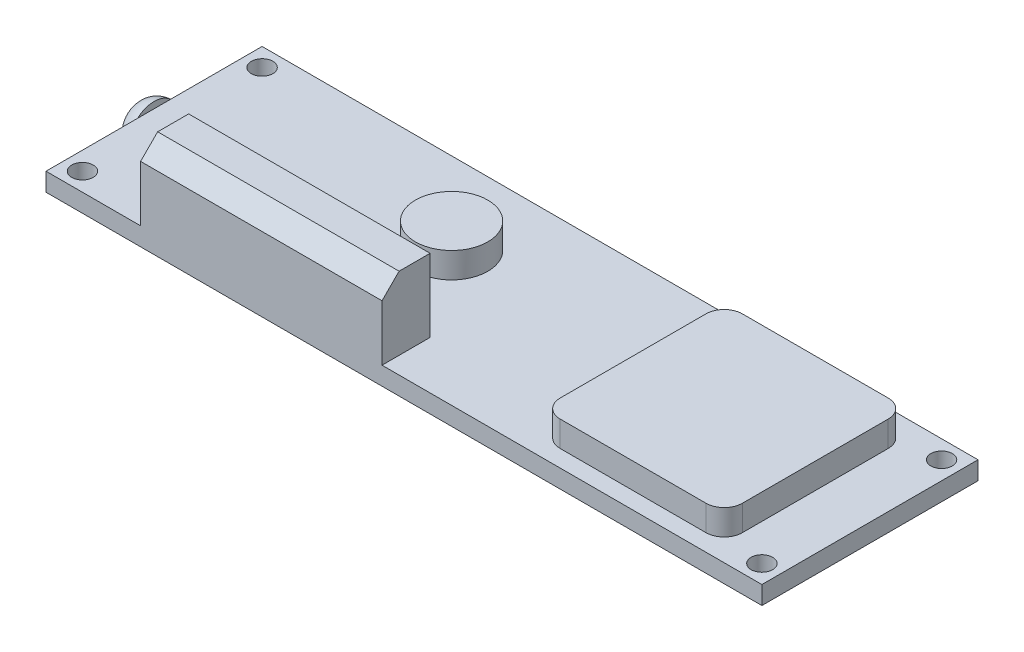
SolidWorks part; units mm, degrees
ref_plane "Front Plane" through (0, 0, 0) normal (0, 0, 1) x (1, 0, 0)
ref_plane "Top Plane" through (0, 0, 0) normal (0, 1, 0) x (1, 0, 0)
ref_plane "Right Plane" through (0, 0, 0) normal (1, 0, 0) x (0, 0, -1)
sketch "Sketch1" plane through (0, 0, 0) normal (0, 1, 0) x (1, 0, 0)
  line L1 (0, 0) -> (99.7966, 0)
  line L2 (0, 0) -> (0, 30.1244)
  line L3 (0, 30.1244) -> (99.7966, 30.1244)
  line L4 (99.7966, 0) -> (99.7966, 30.1244)
  dimension "D1" = 30.1244
  dimension "D2" = 99.7966
extrude "Boss-Extrude1" add sketch "Sketch1" along normal blind 2.54 contours L3 L4 L1 L2
sketch "Sketch2" plane through (0, 2.54, 0) normal (0, 1, 0) x (1, 0, 0)
  line L0 (0, 0) -> (99.7966, 0) construction
  line L1 (13.186, 0) -> (46.8408, 0)
  line L2 (13.186, 0) -> (13.186, 6.7003)
  line L3 (13.186, 6.7003) -> (46.8408, 6.7003)
  line L4 (46.8408, 0) -> (46.8408, 6.7003)
extrude "Boss-Extrude2" add sketch "Sketch2" along normal blind 10.16
sketch "Sketch3" plane through (0, 2.54, 0) normal (0, 1, 0) x (1, 0, 0)
  line L1 (99.7966, 0) -> (99.7966, 30.1244) construction
  line L2 (92.1766, 2.3622) -> (92.1766, 27.7622)
  line L3 (92.1766, 27.7622) -> (66.7766, 27.7622)
  line L4 (66.7766, 27.7622) -> (66.7766, 2.3622)
  line L5 (92.1766, 2.3622) -> (66.7766, 2.3622)
  circle A0 centre (37.8344, 18.7074) radius 5.0456
  point P9 (66.7766, 15.0622)
  point P10 (92.1766, 15.0622)
  dimension "D1" = 25.4
  dimension "D2" = 25.4
  dimension "D3" = 7.62
extrude "Boss-Extrude3" add sketch "Sketch3" along normal blind 3.556
fillet "Fillet1" radius 2.54 4 edges at (92.1766, 4.318, -27.7622) (66.7766, 4.318, -27.7622) (92.1766, 4.318, -2.3622) (66.7766, 4.318, -2.3622)
sketch "Sketch4" plane through (0, 0, 0) normal (-1, 0, 0) x (0, 0, 1)
  line L0 (0, 0) -> (-30.1244, 0) construction
  circle A0 centre (-15.0622, 0) radius 3.429
  dimension "D1" = 6.858
extrude "Boss-Extrude4" add sketch "Sketch4" along normal blind 2.54
fillet "Fillet2" radius 2.54 1 edges at (-2.54, 0, -11.6332)
chamfer "Chamfer1" distance 2.38 angle 45 1 edges at (30.0134, 12.7, 0)
sketch "Sketch5" plane through (0, 2.54, 0) normal (0, 1, 0) x (1, 0, 0)
  text T0 "AIM XTRA\r\n"
extrude "Cut-Extrude1" cut sketch "Sketch5" against normal blind 0.762
ref_plane "Plane1" through (0, 0, -15.0622) normal (0, 0, 1) x (1, 0, 0)
ref_plane "Plane2" through (49.8983, 0, 0) normal (-1, 0, 0) x (0, 0, 1)
hole_wizard "Ø1.5mm Dowel Hole1" positions "Sketch7" profile "Sketch9" hole size "Ø1.5" standard "AS"
sketch "Sketch7" plane through (0, 2.54, 0) normal (0, 1, 0) x (1, 0, 0)
  line L0 (99.7966, 0) -> (99.7966, 30.1244) construction
  line L1 (46.8408, 0) -> (99.7966, 0) construction
  point P0 (97.2566, 2.54)
  dimension "D1" = 2.54
  dimension "D2" = 2.54
sketch "Sketch9" plane through (97.2566, 2.54, -2.54) normal (1, 0, 0) x (0, 0, 1)
  line L0 (0, 0) -> (0, 3.4413)
  line L1 (0, 3.4413) -> (1.5, 2.54)
  line L2 (1.5, 2.54) -> (1.5, 0)
  line L5 (1.5, 0) -> (0, 0)
  line L10 (0, 3.4413) -> (-1.5, 2.54) construction
  line L11 (0, -6.35) -> (0, 107.95) construction
  dimension "Hole Dia." = 3
  dimension "Hole Depth" = 2.54
  dimension "Drill Angle" = 118
mirror "Mirror1" about plane through (0, 0, -15.0622) normal (0, 0, 1) of "Ø1.5mm Dowel Hole1"
mirror "Mirror2" about plane through (49.8983, 0, 0) normal (-1, 0, 0) of "Ø1.5mm Dowel Hole1", "Mirror1"
